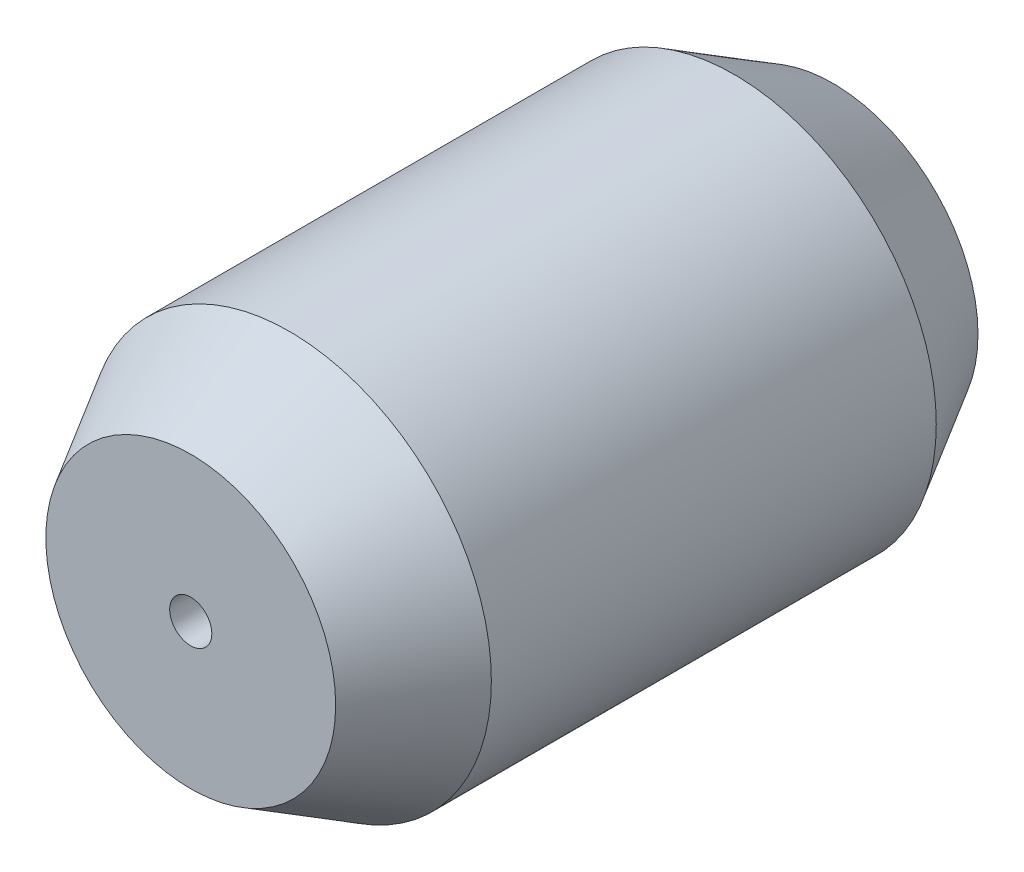
SolidWorks part; units mm, degrees
material "ALUMINUM 6061-T6; 6061-T651"
ref_plane "Front Plane" through (0, 0, 0) normal (0, 0, 1) x (1, 0, 0)
ref_plane "Top Plane" through (0, 0, 0) normal (0, 1, 0) x (1, 0, 0)
ref_plane "Right Plane" through (0, 0, 0) normal (1, 0, 0) x (0, 0, -1)
sketch "Sketch1" plane through (0, 0, 0) normal (0, 0, 1) x (1, 0, 0)
  circle A0 centre (0, 0) radius 9.7409
  circle A1 centre (0, 0) radius 1.016
  dimension "D1" = 19.4818
  dimension "D2" = 2.032
extrude "Boss-Extrude1" add sketch "Sketch1" along normal blind 15.494 and the other way blind 15.494
chamfer "Chamfer2" distance 4.7625 angle 30 1 edges at (9.7409, 0, -15.494) first distance on face at (9.7409, 0, -15.494)
chamfer "Chamfer3" distance 4.7625 angle 30 1 edges at (9.7409, 0, 15.494) first distance on face at (9.7409, 0, -10.7315)
sketch "Sketch2" plane through (0, 0, 0) normal (0, 1, 0) x (1, 0, 0)
  line L0 (9.7409, -10.7315) -> (-9.7409, -10.7315) construction
  line L1 (-6.9913, -15.494) -> (6.9913, -15.494) construction
  line L2 (9.7409, 10.7315) -> (-9.7409, 10.7315) construction
  line L3 (6.9913, 15.494) -> (-6.9913, 15.494) construction
  line L4 (9.7409, -10.7315) -> (-9.7409, -10.7315)
  line L5 (-6.9913, -15.494) -> (6.9913, -15.494)
  line L6 (9.7409, 10.7315) -> (-9.7409, 10.7315)
  line L7 (6.9913, 15.494) -> (-6.9913, 15.494)
  dimension "D1" = 30.988
  dimension "D2" = 21.463
  dimension "D3" = 19.4818
  dimension "D4" = 13.9825
